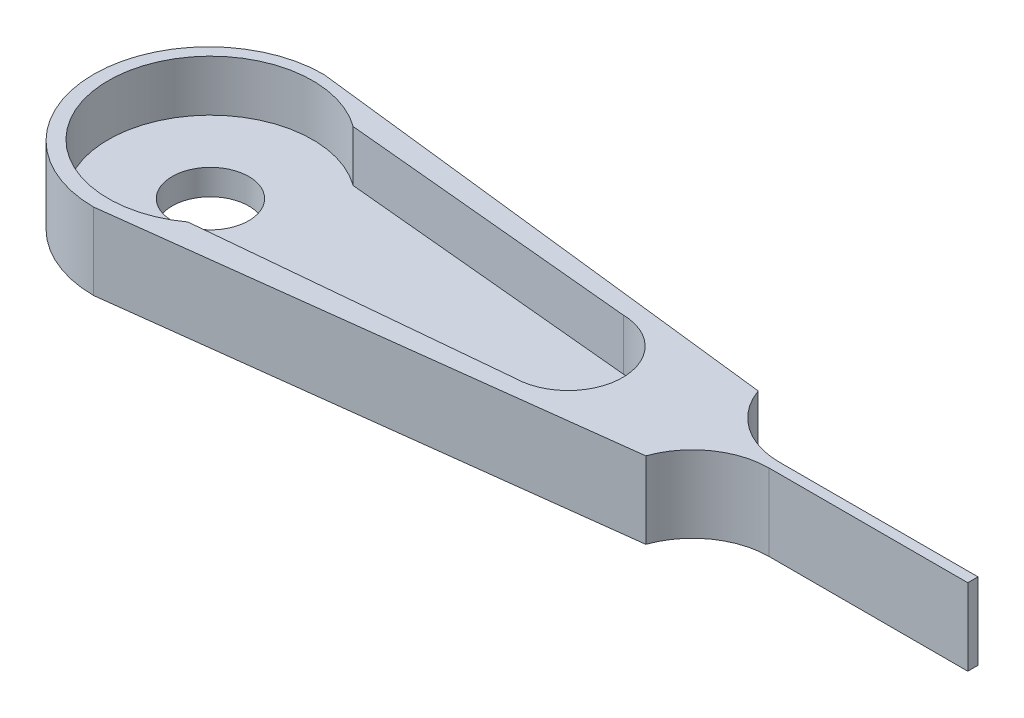
SolidWorks part; units mm, degrees
ref_plane "Front Plane" through (0, 0, 0) normal (0, 0, 1) x (1, 0, 0)
ref_plane "Top Plane" through (0, 0, 0) normal (0, 1, 0) x (1, 0, 0)
ref_plane "Right Plane" through (0, 0, 0) normal (1, 0, 0) x (0, 0, -1)
sketch "Sketch2" plane through (0, 0, 0) normal (0, 1, 0) x (1, 0, 0)
  line L0 (-24.822, 2.75) -> (-24.822, -2.75) construction
  line L1 (-26.9871, 0) -> (-9.8477, 0) construction
  line L2 (-7.7497, -2.2) -> (-7.7497, -0.2)
  line L3 (-7.7497, -0.2) -> (2.8515, -0.2)
  line L4 (-26.9871, 4.4284) -> (-14.9978, 3.0396)
  line L5 (-7.7497, -2.2) -> (-26.9871, -4.5716)
  line L6 (-26.9871, 0) -> (-1.9871, 0) construction
  line L7 (-26.9871, -4.5716) -> (-2.2995, -1.5281) construction
  line L8 (-26.9871, 4.4284) -> (-7.7497, 2.2) construction
  line L9 (2.8515, -0.2) -> (2.8515, 0.2)
  line L10 (-14.9978, 3.0396) -> (-7.7497, 2.2)
  line L11 (-24.775, 3.2478) -> (-12.94, 2.1284)
  line L12 (-12.94, -2.1284) -> (-24.775, -3.2478)
  line L13 (2.8515, 0.2) -> (-7.7497, 0.2)
  line L14 (-7.7497, 0.2) -> (-7.7497, 2.2)
  circle A1 centre (-26.9871, 0) radius 1.5
  circle A3 centre (-26.9871, -0.0716) radius 4.5
  circle A4 centre (-12.9871, -0.0716) radius 2.6306
  circle A6 centre (-12.9871, 0) radius 2.1306
  circle A7 centre (-26.9871, 0) radius 4
  dimension "D1" = 5.5
  dimension "D2" = 0.4
  dimension "D3" = 14
  dimension "D4" = 14
  dimension "D7" = 0.2
  dimension "D5" = 2
  dimension "D6" = 2
  dimension "D8" = 29.8387
extrude "Boss-Extrude1" add sketch "Sketch2" along normal blind 1 contours A7 A1 | A7 L12 A3 L11 | A4 L11 A3 L12 | A6 L11 A4 L12 | A6 region at (-19.2239, 0, -0.0168) region at (-24.1739, 0, 3.1225) region at (-15.5625, 0, -0.047) region at (-30.874, 0, 0) region at (-12.9871, 0, 0)
extrude "Boss-Extrude2" add sketch "Sketch2<3>" along normal blind 3 contours L10 L4 A3 L11 A4 L12 L5 | A6 L12 A4 L11 | A7 L11 A3 L4 L5 L12 region at (-16.8588, 0, 3.0196) region at (-26.4552, 0, 4.3862) region at (-13.691, 0, 2.2662)
sketch "Sketch2<3>" plane through (0, 0, 0) normal (0, 1, 0) x (1, 0, 0) same geometry as "Sketch2"
fillet "Fillet1" radius 3 2 edges at (-7.7497, 1.5, 0.2) (-7.7497, 1.5, -0.2)
